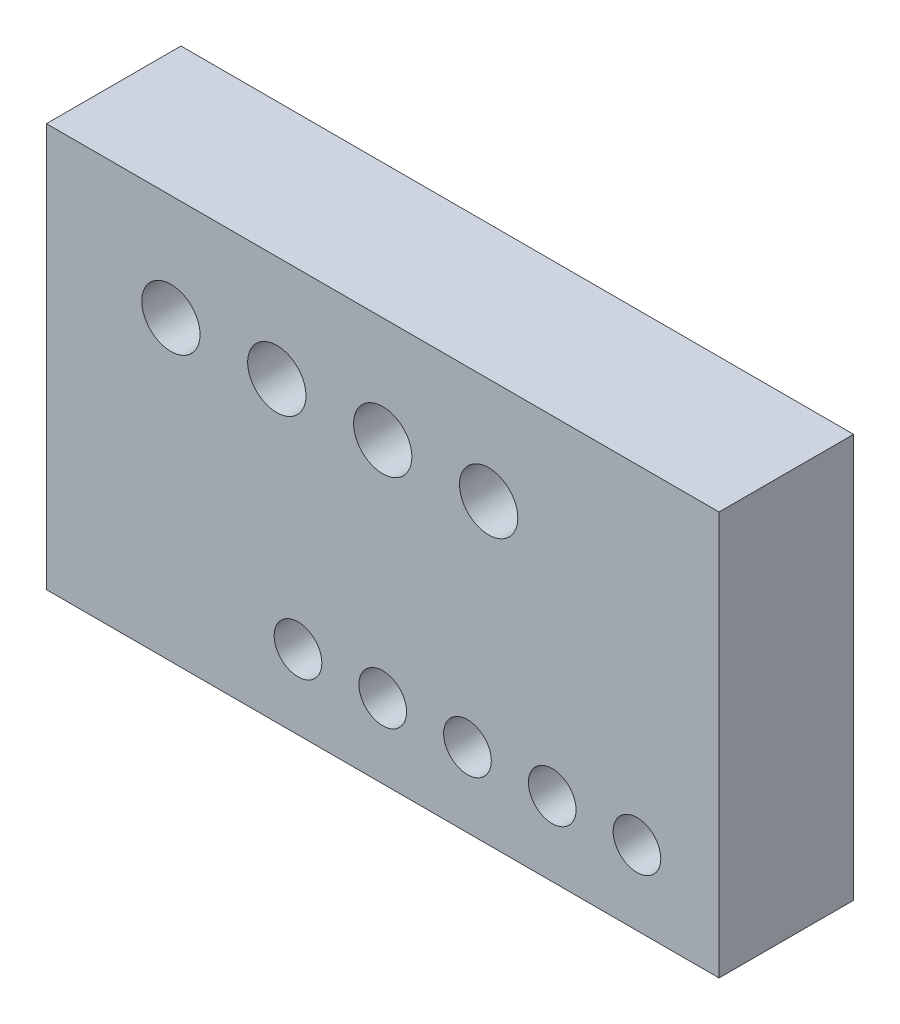
SolidWorks part; units mm, degrees
ref_plane "Front Plane" through (0, 0, 0) normal (0, 0, 1) x (1, 0, 0)
ref_plane "Top Plane" through (0, 0, 0) normal (0, 1, 0) x (1, 0, 0)
ref_plane "Right Plane" through (0, 0, 0) normal (1, 0, 0) x (0, 0, -1)
sketch "Sketch1" plane through (0, 0, 0) normal (0, 0, 1) x (1, 0, 0)
  line L1 (31.75, -19.05) -> (-31.75, -19.05)
  line L2 (31.75, -19.05) -> (31.75, 19.05)
  line L3 (31.75, 19.05) -> (-31.75, 19.05)
  line L4 (-31.75, -19.05) -> (-31.75, 19.05)
  line L5 (31.75, -19.05) -> (-31.75, 19.05) construction
  line L6 (31.75, 19.05) -> (-31.75, -19.05) construction
  point P0 (0, 0)
  point P6 (0, -12.05)
  point P7 (-8, -12.05)
  point P8 (8, -12.05)
  point P9 (16, -12.05)
  point P10 (24, -12.05)
  point P11 (-10, 9.05)
  point P12 (0, 9.05)
  point P13 (10, 9.05)
  point P14 (-20, 9.05)
  point P15 (-17, 9.7531)
  point P16 (-31.75, 10.0312)
  point P17 (0, 0)
  point P18 (0, 0)
  point P19 (7.7453, -17.4)
  point P20 (-9.7441, 11.6969)
  point P21 (0, -17.4)
  point P22 (-15.4225, 13.2868)
  point P23 (0, 12.984)
  point P24 (0, 0)
  point P25 (-27.4482, 15.4)
  point P26 (1.3279, 15.4)
  point P27 (0, 15.4)
  point P28 (0, -17.4)
  point P29 (0, 0)
  point P30 (0, 0)
  point P31 (0, 0)
  point P32 (0, 0)
  point P33 (0, -11.05)
  dimension "D1" = 38.1
  dimension "D2" = 63.5
  dimension "D3" = 8
  dimension "D4" = 8
  dimension "D5" = 8
  dimension "D6" = 8
  dimension "D7" = 7
  dimension "D8" = 10
  dimension "D9" = 10
  dimension "D10" = 10
  dimension "D11" = 10
extrude "Boss-Extrude1" add sketch "Sketch1" along normal blind 12.7
hole_wizard "M4 Clearance Hole1" positions "Sketch2" profile "Sketch3" hole size "M4" standard "ANSI Metric" end condition through all
sketch "Sketch2" plane through (0, 0, 12.7) normal (0, 0, 1) x (1, 0, 0)
  point P0 (-8, -12.05)
  point P3 (0, -12.05)
  point P6 (8, -12.05)
  point P9 (16, -12.05)
  point P12 (24, -12.05)
sketch "Sketch3" plane through (-8, -12.05, 12.7) normal (1, 0, 0) x (0, -1, 0)
  line L0 (0, 0) -> (0, 12.7)
  line L1 (0, 12.7) -> (2.25, 12.7)
  line L2 (2.25, 12.7) -> (2.25, 0)
  line L5 (2.25, 0) -> (0, 0)
  line L11 (0, -6.35) -> (0, 107.95) construction
  dimension "Thru Hole Dia." = 4.5
  dimension "Thru Hole Depth" = 12.7
hole_wizard "M5 Clearance Hole1" positions "Sketch4" profile "Sketch5" hole size "M5" standard "ANSI Metric" end condition through all
sketch "Sketch4" plane through (0, 0, 12.7) normal (0, 0, 1) x (1, 0, 0)
  point P0 (-20, 9.05)
  point P3 (-10, 9.05)
  point P6 (0, 9.05)
  point P9 (10, 9.05)
sketch "Sketch5" plane through (-20, 9.05, 12.7) normal (1, 0, 0) x (0, -1, 0)
  line L0 (0, 0) -> (0, 12.7)
  line L1 (0, 12.7) -> (2.75, 12.7)
  line L2 (2.75, 12.7) -> (2.75, 0)
  line L5 (2.75, 0) -> (0, 0)
  line L11 (0, -6.35) -> (0, 107.95) construction
  dimension "Thru Hole Dia." = 5.5
  dimension "Thru Hole Depth" = 12.7
